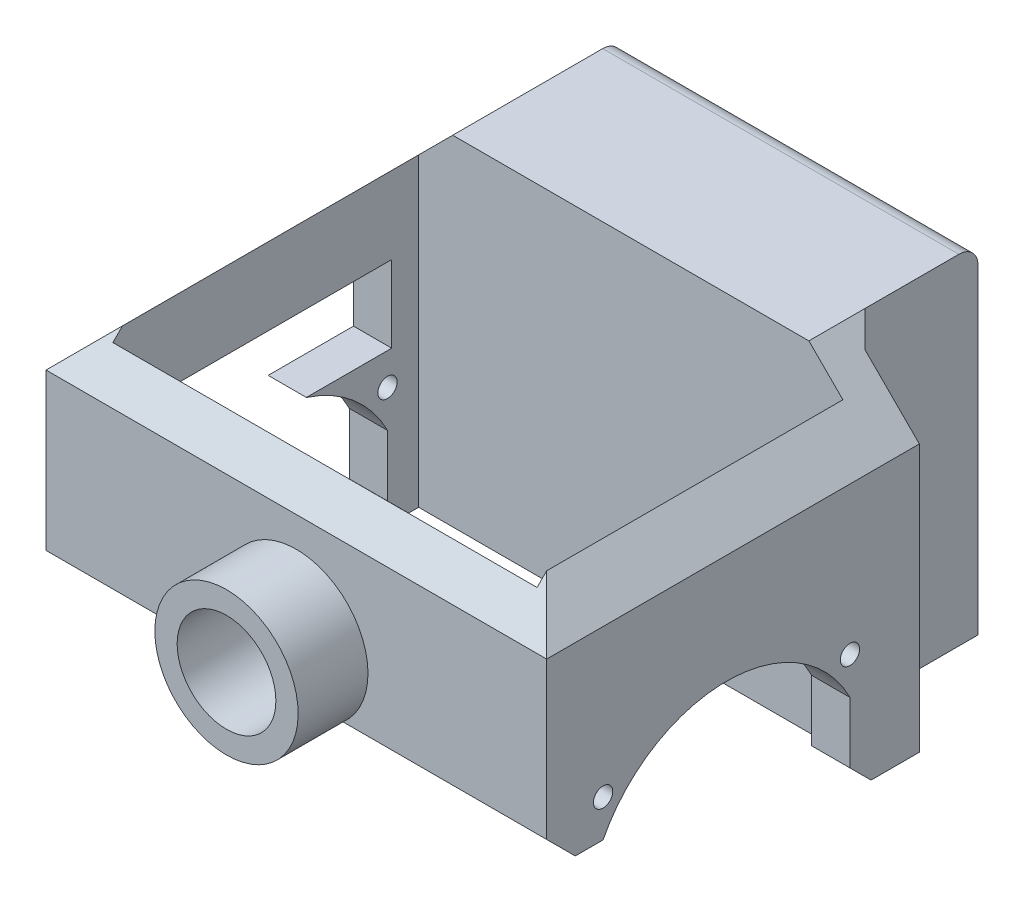
SolidWorks part; units mm, degrees
material "PLA"
ref_plane "Front Plane" through (0, 0, 0) normal (0, 0, 1) x (1, 0, 0)
ref_plane "Top Plane" through (0, 0, 0) normal (0, 1, 0) x (1, 0, 0)
ref_plane "Right Plane" through (0, 0, 0) normal (1, 0, 0) x (0, 0, -1)
sketch "Sketch1" plane through (0, 0, 0) normal (1, 0, 0) x (0, 0, -1)
  line L1 (0, 0) -> (25, 0)
  line L2 (0, 0) -> (0, 30)
  line L3 (0, 30) -> (25, 30)
  line L4 (25, 0) -> (25, 30)
  dimension "D1" = 30
  dimension "D2" = 25
extrude "Boss-Extrude1" add sketch "Sketch1" along normal blind 3.175
sketch "Sketch2" plane through (0, 0, 0) normal (-1, 0, 0) x (0, 0, 1)
  line L1 (-25, 30) -> (0, 30)
  line L2 (-25, 30) -> (-25, 33.175)
  line L3 (-25, 33.175) -> (0, 33.175)
  line L4 (0, 30) -> (0, 33.175)
  dimension "D1" = 3.175
extrude "Boss-Extrude2" add sketch "Sketch2" against normal blind 41.58
sketch "Sketch3" plane through (0, 30, 0) normal (0, -1, 0) x (1, 0, 0)
  line L0 (41.58, 0) -> (3.175, 0) construction
  line L1 (41.58, -25) -> (38.405, -25)
  line L2 (41.58, -25) -> (41.58, 0)
  line L3 (41.58, 0) -> (38.405, 0)
  line L4 (38.405, -25) -> (38.405, 0)
  dimension "D1" = 3.175
extrude "Boss-Extrude3" add sketch "Sketch3" along normal up to surface (30 mm away) up to face at (1.5875, 0, -12.5)
sketch "Sketch4" plane through (0, 0, 0) normal (-1, 0, 0) x (0, 0, 1)
  circle A0 centre (-12.36, -5.21) radius 11.5
  dimension "D1" = 23
extrude "Cut-Extrude1" cut sketch "Sketch4" against normal up to next
sketch "Sketch5" plane through (0, 0, 0) normal (-1, 0, 0) x (0, 0, 1)
  circle A0 centre (-22.61, 3.09) radius 0.8
  circle A1 centre (-22.61, 23.79) radius 0.8
  circle A2 centre (-2.11, 23.79) radius 0.8
  circle A3 centre (-2.11, 3.09) radius 0.8
extrude "Cut-Extrude2" cut sketch "Sketch5" against normal up to next
sketch "Sketch6" plane through (41.58, 0, 0) normal (1, 0, 0) x (0, 0, -1)
  line L1 (1.76, 5.74) -> (22.96, 5.74)
  line L2 (1.76, 5.74) -> (1.76, 12.115)
  line L3 (1.76, 12.115) -> (22.96, 12.115)
  line L4 (22.96, 5.74) -> (22.96, 12.115)
  circle A0 centre (2.11, 3.09) radius 0.8
  circle A1 centre (22.61, 3.09) radius 0.8
  circle A2 centre (22.61, 27.54) radius 0.7999
  circle A3 centre (2.11, 27.54) radius 0.8
extrude "Cut-Extrude3" cut sketch "Sketch6" against normal up to next
sketch "Sketch7" plane through (41.58, 0, 0) normal (1, 0, 0) x (0, 0, -1)
  circle A0 centre (12.36, -5.21) radius 11.5
  dimension "D1" = 23
extrude "Cut-Extrude4" cut sketch "Sketch7" against normal up to next
sketch "Sketch8" plane through (0, 0, 0) normal (0, 0, 1) x (1, 0, 0)
  line L8 (0, 33.175) -> (0, 0)
  line L9 (0, 0) -> (3.175, 0)
  line L10 (3.175, 0) -> (3.175, 30)
  line L11 (3.175, 30) -> (38.405, 30)
  line L12 (38.405, 30) -> (38.405, 0)
  line L13 (38.405, 0) -> (41.58, 0)
  line L14 (41.58, 0) -> (41.58, 33.175)
  line L15 (41.58, 33.175) -> (0, 33.175)
  line L16 (0, 33.175) -> (0, 0)
  line L17 (0, 0) -> (3.175, 0)
  line L18 (3.175, 0) -> (3.175, 30)
  line L19 (3.175, 30) -> (38.405, 30)
  line L20 (38.405, 30) -> (38.405, 0)
  line L21 (38.405, 0) -> (41.58, 0)
  line L22 (41.58, 0) -> (41.58, 33.175)
  line L23 (41.58, 33.175) -> (0, 33.175)
  dimension "D1" = 0
extrude "Boss-Extrude4" add sketch "Sketch8" along normal blind 0.2
sketch "Sketch9" plane through (0, 0, 0.2) normal (0, 0, 1) x (1, 0, 0)
  line L1 (0, 0) -> (41.58, 0)
  line L2 (0, 0) -> (0, 33.175)
  line L3 (0, 33.175) -> (41.58, 33.175)
  line L4 (41.58, 0) -> (41.58, 33.175)
extrude "Boss-Extrude5" add sketch "Sketch9" along normal blind 3.175
sketch "Sketch10" plane through (0, 0, -25) normal (0, 0, -1) x (-1, 0, 0)
  line L8 (0, 0) -> (0, 33.175)
  line L9 (0, 33.175) -> (-41.58, 33.175)
  line L10 (-41.58, 33.175) -> (-41.58, 0)
  line L11 (-41.58, 0) -> (-38.405, 0)
  line L12 (-38.405, 0) -> (-38.405, 30)
  line L13 (-38.405, 30) -> (-3.175, 30)
  line L14 (-3.175, 30) -> (-3.175, 0)
  line L15 (-3.175, 0) -> (0, 0)
  line L16 (0, 0) -> (0, 33.175)
  line L17 (0, 33.175) -> (-41.58, 33.175)
  line L18 (-41.58, 33.175) -> (-41.58, 0)
  line L19 (-41.58, 0) -> (-38.405, 0)
  line L20 (-38.405, 0) -> (-38.405, 30)
  line L21 (-38.405, 30) -> (-3.175, 30)
  line L22 (-3.175, 30) -> (-3.175, 0)
  line L23 (-3.175, 0) -> (0, 0)
  dimension "D1" = 0
extrude "Boss-Extrude6" add sketch "Sketch10" along normal blind 0.2
sketch "Sketch11" plane through (0, 0, -25.2) normal (0, 0, -1) x (-1, 0, 0)
  line L1 (-41.58, 0) -> (0, 0)
  line L2 (-41.58, 0) -> (-41.58, 33.175)
  line L3 (-41.58, 33.175) -> (0, 33.175)
  line L4 (0, 0) -> (0, 33.175)
extrude "Boss-Extrude7" add sketch "Sketch11" along normal blind 3.175
chamfer "Chamfer1" distance 3.175 angle 45 2 edges at (20.79, 33.175, 3.375) (20.79, 33.175, -28.375)
chamfer "Chamfer2" distance 3.175 angle 45 1 edges at (20.79, 0, 3.375)
sketch "Sketch13" plane through (0, 0, -28.375) normal (0, 0, -1) x (-1, 0, 0)
  line L0 (0, 0) -> (0, 30) construction
  line L1 (-35.58, 18.175) -> (-6, 18.175)
  line L3 (-35.58, 21.35) -> (-6, 21.35)
  line L5 (-35.58, 21.35) -> (-35.58, 18.175)
  line L6 (-6, 21.35) -> (-6, 18.175)
  line L7 (-41.58, 30) -> (-41.58, 0) construction
  line L8 (-41.58, 0) -> (0, 0) construction
  dimension "D1" = 3.175
  dimension "D2" = 6
  dimension "D3" = 6
  dimension "D5" = 18.175
extrude "Boss-Extrude8" add sketch "Sketch13" along normal blind 7.695
sketch "Sketch14" plane through (0, 18.175, 0) normal (0, -1, 0) x (1, 0, 0)
  line L0 (35.58, -35.745) -> (35.58, -39.2524) construction
  line L1 (-0.7092, -39.245) -> (9.3147, -39.245) construction
  line L7 (6, -35.745) -> (6, -39.245)
  line L8 (6, -39.245) -> (35.58, -39.245)
  line L9 (35.58, -35.745) -> (35.58, -39.245)
  line L11 (35.58, -36.07) -> (6, -36.07) construction
  line L12 (6, -35.745) -> (35.58, -35.745)
  dimension "D1" = 3.5
  dimension "D2" = 3.175
  dimension "D3" = 3.5
extrude "Boss-Extrude9" add sketch "Sketch14" against normal up to surface and the other way blind 25 up to face at (20.79, 21.35, -32.2225)
fillet "Fillet1" radius 1.5875 2 edges at (20.79, 21.35, -39.245) (20.79, 18.175, -35.745)
fillet "Fillet2" radius 1.5875 1 edges at (20.79, 21.35, -28.375)
sketch "Sketch16" plane through (0, 0, -39.245) normal (0, 0, -1) x (-1, 0, 0)
  line L0 (-20.79, 19.7625) -> (-20.79, 6.9025) construction
  line L1 (-6, 19.7625) -> (-35.58, 19.7625) construction
  circle A0 centre (-20.79, 6.9025) radius 7.1
  dimension "D2" = 14.2
  dimension "D1" = 12.86
extrude "Cut-Extrude5" cut sketch "Sketch16" against normal up to next
sketch "Sketch20" plane through (0, 0, -35.745) normal (0, 0, 1) x (1, 0, 0)
  circle A0 centre (20.79, 6.9025) radius 7.1 construction
  circle A1 centre (20.79, 6.9025) radius 7.1 construction
  circle A2 centre (20.79, 6.9025) radius 4.1
  circle A3 centre (20.79, 6.9025) radius 8
  dimension "D1" = 8.2
  dimension "D2" = 16
extrude "Boss-Extrude11" add sketch "Sketch20" along normal blind 5
sketch "Sketch21" plane through (0, -6.825, 0) normal (0, -1, 0) x (1, 0, 0)
  line L0 (20.79, -30.745) -> (20.79, -35.745) construction
  line L1 (28.79, -30.745) -> (12.79, -30.745) construction
  line L2 (35.58, -35.745) -> (6, -35.745) construction
  circle A0 centre (20.79, -33.245) radius 1.025
  dimension "D1" = 2.05
extrude "Cut-Extrude6" cut sketch "Sketch21" against normal up to surface (25 mm away)
sketch "Sketch23" plane through (0, 0, 3.375) normal (0, 0, 1) x (1, 0, 0)
  circle A2 centre (20.79, 6.9025) radius 4.1
  circle A4 centre (20.79, 6.9025) radius 5.95
  dimension "D1" = 8.2
  dimension "D2" = 11.9
extrude "Boss-Extrude12" add sketch "Sketch23" against normal blind 1.2 and the other way blind 5
sketch "Sketch35" plane through (0, 0, 3.375) normal (0, 0, 1) x (1, 0, 0)
  line L2 (-5.1278, 22.1078) -> (51.5468, 22.1078)
  line L3 (-5.1278, 22.1078) -> (-5.1278, -10.1254)
  line L36 (-5.1278, -10.1254) -> (51.5468, -10.1254)
  line L37 (51.5468, 22.1078) -> (51.5468, -10.1254)
  circle A0 centre (20.79, 6.9025) radius 5.95 construction
  circle A5 centre (20.79, 6.9025) radius 5.95
extrude "Cut-Extrude9" cut sketch "Sketch35" against normal blind 0.8
chamfer "Chamfer4" distance 1.5 angle 45 3 edges at (6, 20.5563, -28.375) (35.58, 20.5563, -28.375) (20.79, 18.175, -28.375)
sketch "Sketch24" plane through (0, 0, -39.245) normal (0, 0, -1) x (-1, 0, 0)
  circle A0 centre (-20.79, 6.9025) radius 10
  circle A1 centre (-20.79, 6.9025) radius 11.5
  dimension "D1" = 20
  dimension "D2" = 1.5
extrude "Boss-Extrude13" add sketch "Sketch24" along normal blind 1.8
sketch "Sketch25" plane through (0, 33.175, 0) normal (0, 1, 0) x (1, 0, 0)
  line L1 (-26.6251, 41.8741) -> (81.4802, 41.8741)
  line L2 (-26.6251, 41.8741) -> (-26.6251, -21.7172)
  line L3 (-26.6251, -21.7172) -> (81.4802, -21.7172)
  line L4 (81.4802, 41.8741) -> (81.4802, -21.7172)
extrude "Cut-Extrude7" cut sketch "Sketch25" against normal up to surface (11.825 mm away) up to face at (20.79, 21.35, -33.81)
chamfer "Chamfer5" distance 6 angle 45 3 edges at (41.58, 21.35, -12.9) (0, 21.35, -12.9) (20.79, 21.35, 2.575)
sketch "Sketch26" plane through (0, 0, 3.375) normal (0, 0, 1) x (1, 0, 0)
  circle A0 centre (20.79, 6.9025) radius 4.1
extrude "Cut-Extrude8" cut sketch "Sketch26" against normal up to surface (3.175 mm away) up to face at (20.79, 8.8625, 0.2)
sketch "Sketch27" plane through (0, 0, 2.175) normal (0, 0, -1) x (-1, 0, 0)
  line L1 (-17.455, 1.975) -> (-24.125, 1.975)
  line L2 (-17.455, 1.975) -> (-24.125, 1.975)
  arc A1 (-24.125, 1.975) -> (-17.455, 1.975) centre (-20.79, 6.9025) ccw
  arc A2 (-24.125, 1.975) -> (-17.455, 1.975) centre (-20.79, 6.9025) ccw
  dimension "D1" = 0
extrude "Boss-Extrude14" add sketch "Sketch27" along normal up to surface (1.975 mm away) up to face at (16.69, 6.9025, 0.2)
sketch "Sketch29" plane through (0, 0, -35.745) normal (0, 0, -1) x (-1, 0, 0)
  circle A0 centre (-20.79, 6.9025) radius 4.1 construction
  circle A1 centre (-20.79, 6.9025) radius 7.1
  circle A2 centre (-20.79, 6.9025) radius 7.1
  circle A3 centre (-20.79, 6.9025) radius 4.1
  dimension "D1" = 0
extrude "Boss-Extrude16" add sketch "Sketch29" along normal up to surface (3.5 mm away) up to face at (13.69, 6.9025, -39.245)
sketch "Sketch31" plane through (0, 0, -35.745) normal (0, 0, 1) x (1, 0, 0)
  line L0 (35.58, -6.825) -> (6, -6.825) construction
  line L2 (6, 16.5875) -> (6, -6.825)
  line L3 (6, -6.825) -> (9.175, -6.825)
  line L4 (9.175, 16.5875) -> (9.175, -6.825)
  line L7 (35.58, 16.5875) -> (35.58, -6.825)
  line L8 (35.58, -6.825) -> (32.405, -6.825)
  line L9 (32.405, 16.5875) -> (32.405, -6.825)
  line L12 (6, 16.5875) -> (6, 20.014)
  line L13 (6, 20.014) -> (9.175, 20.014)
  line L14 (9.175, 16.5875) -> (9.175, 20.014)
  line L16 (32.405, 16.5875) -> (32.405, 20.014)
  line L17 (32.405, 20.014) -> (35.58, 20.014)
  line L18 (35.58, 16.5875) -> (35.58, 20.014)
  line M10 (35.58, -6.825) -> (35.58, 16.5875)
  line M11 (35.58, 16.5875) -> (6, 16.5875)
  line M12 (6, 16.5875) -> (6, -6.825)
  line M13 (6, -6.825) -> (35.58, -6.825)
  dimension "D1" = 3.175
  dimension "D2" = 3.175
extrude "Boss-Extrude17" add sketch "Sketch31" along normal up to surface (7.37 mm away) contours L4 M11 M12 M13 | L9 M11 M13 M10 up to face at (20.79, 12.9687, -28.375)
sketch "Sketch33" plane through (0, 0, 0) normal (0, -1, 0) x (1, 0, 0)
  line L12 (3.175, -25.2) -> (3.175, -22.6121)
  line L13 (3.175, -22.6121) -> (0, -22.6121)
  line L14 (0, -22.6121) -> (0, -28.375)
  line L15 (0, -28.375) -> (6, -28.375)
  line L16 (6, -28.375) -> (9.175, -28.375)
  line L17 (9.175, -28.375) -> (32.405, -28.375)
  line L18 (32.405, -28.375) -> (35.58, -28.375)
  line L19 (35.58, -28.375) -> (41.58, -28.375)
  line L20 (41.58, -28.375) -> (41.58, -22.6121)
  line L21 (41.58, -22.6121) -> (38.405, -22.6121)
  line L22 (38.405, -22.6121) -> (38.405, -25.2)
  line L23 (38.405, -25.2) -> (3.175, -25.2)
  line L24 (3.175, -25.2) -> (3.175, -22.6121)
  line L25 (3.175, -22.6121) -> (0, -22.6121)
  line L26 (0, -22.6121) -> (0, -28.375)
  line L27 (0, -28.375) -> (6, -28.375)
  line L28 (6, -28.375) -> (9.175, -28.375)
  line L29 (9.175, -28.375) -> (32.405, -28.375)
  line L30 (32.405, -28.375) -> (35.58, -28.375)
  line L31 (35.58, -28.375) -> (41.58, -28.375)
  line L32 (41.58, -28.375) -> (41.58, -22.6121)
  line L33 (41.58, -22.6121) -> (38.405, -22.6121)
  line L34 (38.405, -22.6121) -> (38.405, -25.2)
  line L35 (38.405, -25.2) -> (3.175, -25.2)
  dimension "D1" = 0
extrude "Boss-Extrude18" add sketch "Sketch33" along normal up to surface (6.825 mm away) up to face at (20.79, -6.825, -32.935)
sketch "Sketch34" plane through (0, 0, -30.745) normal (0, 0, 1) x (1, 0, 0)
  circle A1 centre (20.79, 6.9025) radius 8
  circle A2 centre (20.79, 6.9025) radius 8
  dimension "D1" = 0
extrude "Boss-Extrude19" add sketch "Sketch34" along normal up to surface (2.37 mm away) up to face at (20.79, 4.925, -28.375)
chamfer "Chamfer7" distance 3.175 angle 45 2 edges at (20.79, -6.825, -35.745) (20.79, -6.825, -28.375)
chamfer "Chamfer8" distance 1.75 angle 45 2 edges at (1.5875, -6.825, -22.6121) (39.9925, -6.825, -22.6121)
ref_plane "Plane1" through (51.58, 0, 0) normal (1, 0, 0) x (0, 0, -1)
mirror "Mirror1" about plane through (51.58, 0, 0) normal (1, 0, 0) of bodies 127
delete or keep bodies "Body-Delete/Keep 1" type delete bodies bodies 127
